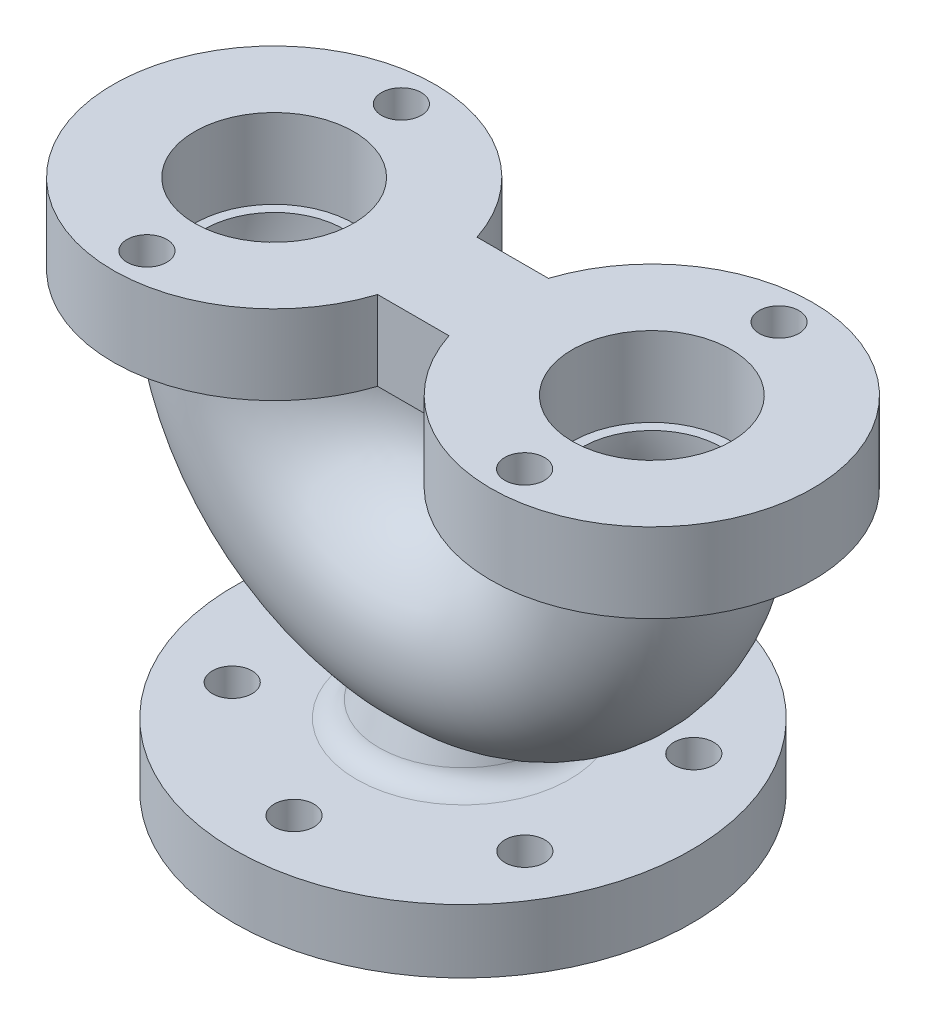
SolidWorks part; units mm, degrees
note: The reader was unsure of these and kept them because the rebuilt part matched: shared geometry of "Sketch2<6>".
other "Markup1"
sketch "Sketch8" plane through (176, 220, 0) normal (0.2207, 0.8326, 0.508) x (0.9753, -0.1929, -0.1075)
ref_plane "Front Plane" through (0, 0, 0) normal (0, 0, 1) x (1, 0, 0)
ref_plane "Top Plane" through (0, 0, 0) normal (0, 1, 0) x (1, 0, 0)
ref_plane "Right Plane" through (0, 0, 0) normal (1, 0, 0) x (0, 0, -1)
sketch "Sketch1" plane through (0, 0, 0) normal (0, 1, 0) x (1, 0, 0)
  line L0 (0, 0) -> (0, 230)
  arc A0 (0, 230) -> (0, 0) centre (0, 115) cw
  arc A1 (0, 20) -> (0, 40) centre (0, 30) ccw
  arc A2 (0, 30) -> (0, 200) centre (0, 115) ccw construction
  arc A5 (0, 190) -> (0, 210) centre (0, 200) ccw
  circle A6 centre (73.6122, 157.5) radius 10
  circle A7 centre (73.6122, 72.5) radius 10
  arc A8 (-78.0941, 148.5606) -> (-68.1114, 165.8511) centre (-73.6122, 157.5) ccw [skipped]
  arc A9 (-68.1114, 64.1489) -> (-78.0941, 81.4394) centre (-73.6122, 72.5) ccw [skipped]
  point P19 (0, 115)
  dimension "D1" = 115
  dimension "D2" = 20
  dimension "D3" = 85
  dimension "D4" = 6
extrude "Boss-Extrude1" add sketch "Sketch1" along normal blind 32 contours A5 L0 A1 A0 A7 A6
sketch "Sketch2" plane through (0, 0, 0) normal (-1, 0, 0) x (0, 0, 1)
  line L0 (-115, 0) -> (-115, 220)
  line L1 (-40, 0) -> (-190, 0) construction
  line L2 (-153.0285, 52.5373) -> (-160, 32)
  line L3 (-40, 32) -> (-190, 32) construction
  line L4 (-145.9589, 68.6738) -> (-155, 0)
  line L5 (-40, 32) -> (-190, 32)
  line L6 (-40, 0) -> (-190, 0)
  arc A0 (-115, 35) -> (-148.6753, 48.0409) centre (-115, 85) ccw
  arc A1 (-115, 50) -> (-145.9589, 68.6738) centre (-115, 85) ccw
  circle A2 centre (-115, 85) radius 35 construction
  circle A3 centre (-115, 85) radius 50 construction
  point P8 (-160, 32)
  point P9 (-160, 32)
  point P12 (-155, 0)
  dimension "D7" = 100
  dimension "D1" = 220
  dimension "D2" = 18.75
  dimension "D3" = 45
  dimension "D4" = 7.5
  dimension "D5" = 40
  dimension "D6" = 85
  dimension "D8" = 15
revolve "Revolve1" add sketch "Sketch2" angle 180 about L0 reverse direction yes
ref_plane "Plane2" through (0, 0, -115) normal (0, 0, 1) x (1, 0, 0)
fillet "Fillet1" radius 12 1 edges at (45, 32, -115)
revolve "Cut-Revolve1" cut sketch "Sketch2<6>" angle 360 about L0
sketch "Sketch2<6>" plane through (0, 0, 0) normal (-1, 0, 0) x (0, 0, 1) same geometry as "Sketch2"
sketch "Sketch3" plane through (0, 0, -115) normal (0, 0, 1) x (1, 0, 0)
  line L0 (0, 32) -> (0, 0) construction
  line L1 (0, 32) -> (0, 0)
  line L2 (0, 85) -> (0, 180) construction
  arc A0 (0, 85) -> (95, 180) centre (0, 180) ccw
  arc A1 (0, 35) -> (145, 180) centre (0, 180) ccw
  arc A2 (0, 135) -> (45, 180) centre (0, 180) ccw
  dimension "D1" = 95
  dimension "D2" = 180
  dimension "D3" = 50
  dimension "D4" = 50
ref_plane "Plane1" through (0, 180, 0) normal (0, 1, 0) x (1, 0, 0)
sketch "Sketch4" plane through (0, 180, 0) normal (0, 1, 0) x (1, 0, 0)
  circle A0 centre (95, 115) radius 50
  circle A1 centre (95, 115) radius 35
  point P0 (95, 115)
  dimension "D1" = 100
  dimension "D2" = 70
sweep "Sweep1" add profiles "Sketch4" path "Sketch3"
sketch "Sketch6" plane through (0, 0, 0) normal (1, 0, 0) x (0, 0, -1)
  line L0 (40, 0) -> (190, 0) construction
  line L1 (115, 0) -> (115, 220) construction
  line L2 (145.9589, 68.6738) -> (155, 0) construction
  line L3 (115, 0) -> (155, 0)
  line L4 (115, 0) -> (115, 50)
  line L5 (145.9589, 68.6738) -> (155, 0)
  circle A0 centre (115, 85) radius 35 construction
  arc A1 (115, 50) -> (145.9589, 68.6738) centre (115, 85) ccw
revolve "Cut-Revolve2" cut sketch "Sketch6" angle 360 about L4
sketch "Sketch7" plane through (0, 180, 0) normal (0, 1, 0) x (1, 0, 0)
  line L0 (95, 115) -> (0, 115) construction
  line L1 (0, 165) -> (0, 65) construction
  line L2 (17.9546, 140) -> (0, 140)
  line L3 (17.9546, 90) -> (0, 90)
  line L4 (0, 140) -> (0, 90)
  arc A0 (17.9546, 90) -> (17.9546, 140) centre (95, 115) ccw
  circle A1 centre (95, 115) radius 50
  circle A2 centre (95, 115) radius 50
  circle A3 centre (95, 115) radius 40
  dimension "D2" = 162
  dimension "D4" = 80
  dimension "D3" = 50
  dimension "D1" = 0
extrude "Boss-Extrude2" add sketch "Sketch7" along normal blind 40 separate body
sketch "Sketch9" plane through (0, 220, 0) normal (0, 1, 0) x (1, 0, 0)
  line L0 (95, 196) -> (95, 34) construction
  line L1 (95, 115) -> (176, 115) construction
  arc A0 (17.9546, 90) -> (17.9546, 140) centre (95, 115) ccw construction
  circle A1 centre (95, 179) radius 10
  circle A2 centre (95, 51) radius 10
  dimension "D1" = 20
  dimension "D2" = 128
extrude "Cut-Extrude1" cut sketch "Sketch9" against normal up to next (40 mm away)
mirror "Mirror1" about plane through (0, 32, 0) normal (-1, 0, 0) of bodies 107 105
